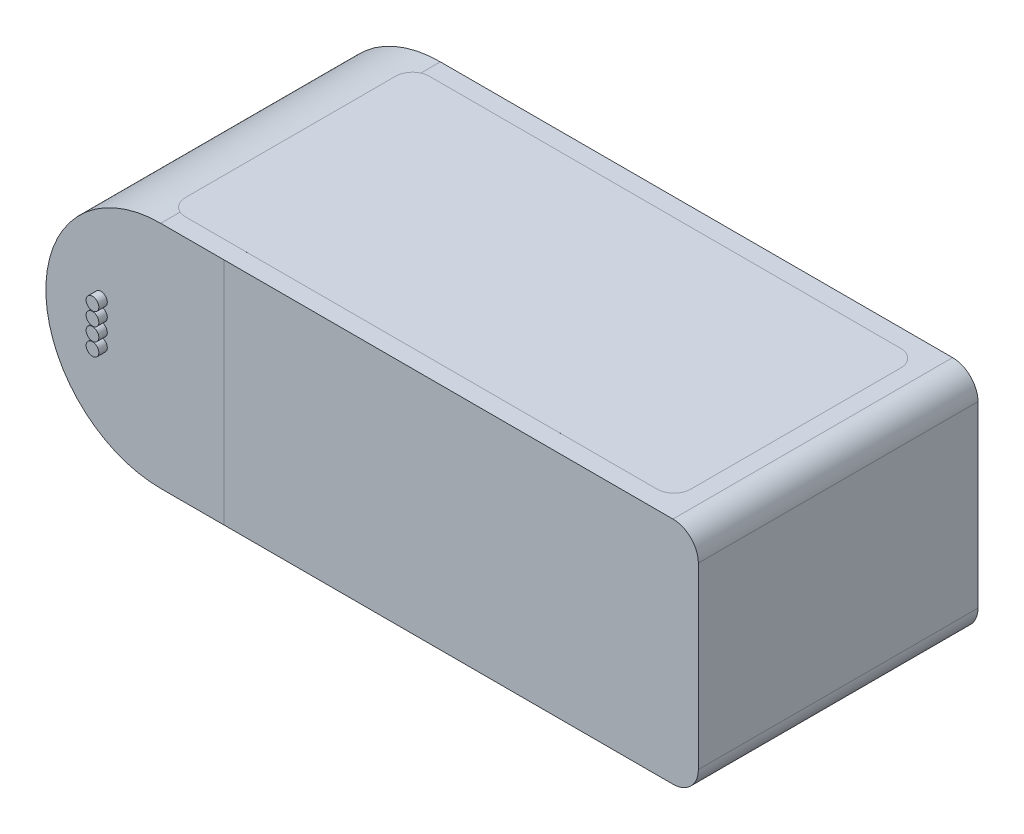
SolidWorks part; units mm, degrees
ref_plane "Front Plane" through (0, 0, 0) normal (0, 0, 1) x (1, 0, 0)
ref_plane "Top Plane" through (0, 0, 0) normal (0, 1, 0) x (1, 0, 0)
ref_plane "Right Plane" through (0, 0, 0) normal (1, 0, 0) x (0, 0, -1)
sketch "Esboço1" plane through (0, 0, 0) normal (0, 1, 0) x (1, 0, 0)
  line L1 (-38.5, -16.5) -> (38.5, -16.5)
  line L2 (-38.5, -16.5) -> (-38.5, 16.5)
  line L3 (-38.5, 16.5) -> (38.5, 16.5)
  line L4 (38.5, -16.5) -> (38.5, 16.5)
  line L5 (-38.5, -16.5) -> (38.5, 16.5) construction
  line L6 (-38.5, 16.5) -> (38.5, -16.5) construction
  point P0 (0, 0)
  dimension "D1" = 33
  dimension "D2" = 77
extrude "Ressalto-extrusão1" add sketch "Esboço1" along normal mid plane 27.1
fillet "Filete1" 2 edges at (-38.5, 13.55, 0) (-38.5, -13.55, 0) type full round first side face at (0, 13.55, 0) second side face at (0, -13.55, 0) middle face at (-38.5, 0, 0)
fillet "Filete2" radius 3 2 edges at (38.5, -13.55, 0) (38.5, 13.55, 0)
sketch "Esboço2" plane through (0, 0, 16.5) normal (0, 0, 1) x (1, 0, 0)
  line L0 (9.3811, 0) -> (-9.3811, 0) construction
  line L1 (-32, -0.775) -> (-32, 0.775) construction
  circle A0 centre (-32, 2.325) radius 0.75
  circle A1 centre (-32, 0.775) radius 0.75
  circle A2 centre (-32, -0.775) radius 0.75
  circle A3 centre (-32, -2.325) radius 0.75
  point P12 (0, 0)
  point P14 (-32, 0)
  dimension "D1" = 1.5
  dimension "D3" = 1.55
  dimension "D4" = 32
  dimension "D2" = 4
extrude "Ressalto-extrusão6" add sketch "Esboço2" along normal blind 1
sketch "Esboço3" plane through (0, 0, -16.5) normal (0, 0, -1) x (-1, 0, 0)
  line L0 (32, 2.325) -> (32, -2.325) construction
  line L1 (18.7, 0) -> (-18.7, 0) construction
  circle A0 centre (32, 2.325) radius 2.05
  circle A1 centre (32, -2.325) radius 2.05
  point P6 (32, 1.9632)
  point P11 (32, 2.2023)
  point P12 (32, 2.4613)
  dimension "D1" = 4.1
extrude "Ressalto-extrusão7" add sketch "Esboço3" along normal blind 2
sketch "Esboço4" plane through (0, 0, 16.5) normal (0, 0, 1) x (1, 0, 0)
  line L0 (-17.5, -13.55) -> (-17.5, 13.55)
  line L1 (-24.95, -13.55) -> (35.5, -13.55) construction
  line L2 (-24.95, 13.55) -> (35.5, 13.55) construction
  line L6 (-24.95, -13.55) -> (35.5, -13.55)
  line L7 (38.5, -10.55) -> (38.5, 10.55)
  line L8 (35.5, 13.55) -> (-24.95, 13.55)
  line L9 (-24.95, -13.55) -> (-17.5, -13.55)
  line L11 (-17.5, 13.55) -> (-24.95, 13.55)
  arc A1 (-24.95, 13.55) -> (-24.95, -13.55) centre (-24.95, 0) ccw construction
  arc A5 (35.5, -13.55) -> (38.5, -10.55) centre (35.5, -10.55) ccw
  arc A6 (38.5, 10.55) -> (35.5, 13.55) centre (35.5, 10.55) ccw
  arc A7 (-24.95, 13.55) -> (-24.95, -13.55) centre (-24.95, 0) ccw
  arc A10 (-24.95, 13.55) -> (-24.95, -13.55) centre (-24.95, 0) ccw
  dimension "D1" = 21
  dimension "D2" = 0
extrude "Ressalto-extrusão8" add sketch "Esboço4" along normal blind 0.001
mirror "Espelhar1" about plane through (0, 0, 0) normal (0, 0, 1) of "Ressalto-extrusão8"
sketch "Esboço6" plane through (0, 13.55, 0) normal (0, 1, 0) x (1, 0, 0)
  line L0 (38.5, 16.5) -> (38.5, -16.5) construction
  line L1 (-24.12, 14.381) -> (31.5, 14.381)
  line L2 (-26.12, 12.381) -> (-26.12, -12.381)
  line L3 (-24.12, -14.381) -> (31.5, -14.381)
  line L4 (33.5, 12.381) -> (33.5, -12.381)
  line L5 (-17.5, -16.501) -> (-24.95, -16.501) construction
  arc A0 (31.5, 14.381) -> (33.5, 12.381) centre (31.5, 12.381) cw
  arc A1 (31.5, -14.381) -> (33.5, -12.381) centre (31.5, -12.381) ccw
  arc A2 (-26.12, -12.381) -> (-24.12, -14.381) centre (-24.12, -12.381) ccw
  arc A3 (-24.12, 14.381) -> (-26.12, 12.381) centre (-24.12, 12.381) ccw
  point P12 (33.5, 0)
  point P14 (0, 0)
  point P15 (-22.2934, 8.3919)
  point P18 (-24.12, 11.8696)
  dimension "D1" = 2
  dimension "D2" = 59.62
  dimension "D3" = 5
  dimension "D4" = 2.12
extrude "Ressalto-extrusão9" add sketch "Esboço6" along normal blind 0.0001
